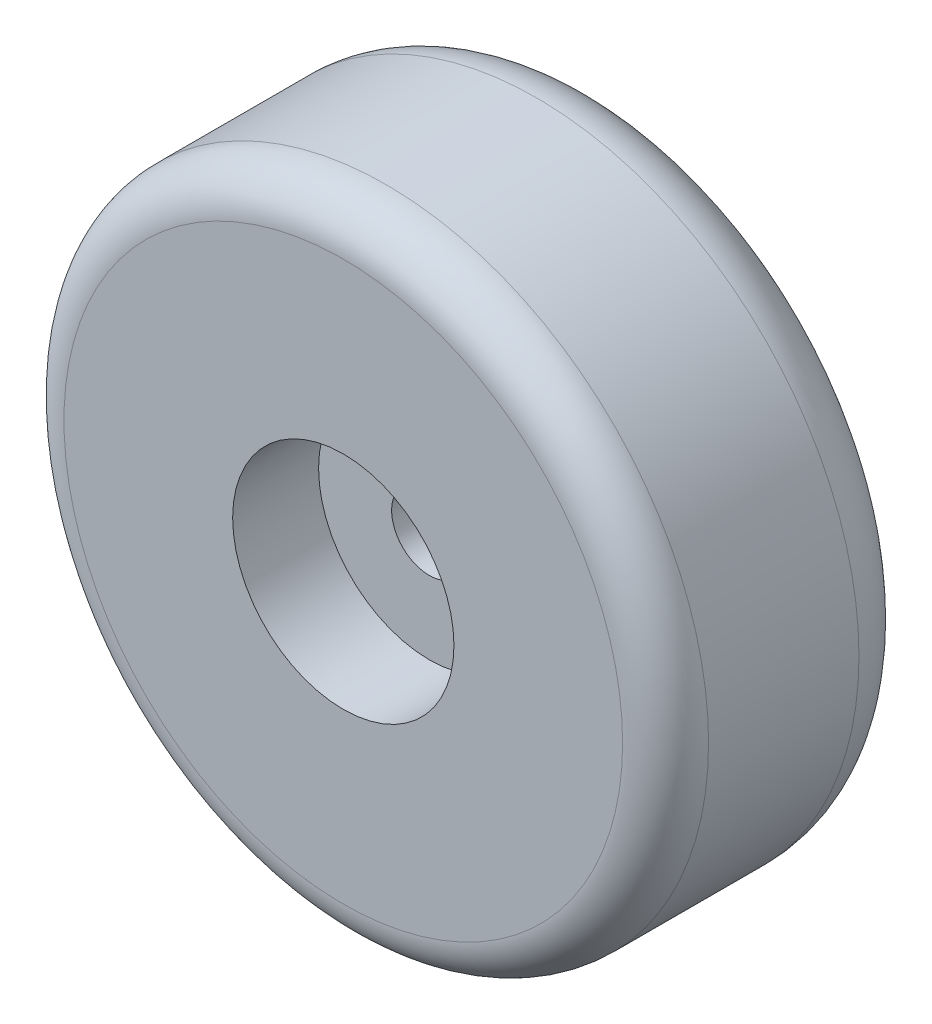
SolidWorks part; units mm, degrees
ref_plane "Спереди" through (0, 0, 0) normal (0, 0, 1) x (1, 0, 0)
ref_plane "Сверху" through (0, 0, 0) normal (0, 1, 0) x (1, 0, 0)
ref_plane "Справа" through (0, 0, 0) normal (1, 0, 0) x (0, 0, -1)
sketch "Эскиз1" plane through (0, 0, 0) normal (0, 0, 1) x (1, 0, 0)
  circle A0 centre (0, 0) radius 1.75
  circle A1 centre (0, 0) radius 15
  dimension "D1" = 3.5
  dimension "D2" = 30
extrude "Бобышка-Вытянуть1" add sketch "Эскиз1" along normal blind 12
sketch "Эскиз2" plane through (0, 0, 12) normal (0, 0, 1) x (1, 0, 0)
  circle A0 centre (0, 0) radius 5.15
  dimension "D1" = 10.3
extrude "Вырез-Вытянуть1" cut sketch "Эскиз2" against normal blind 4
fillet "Скругление1" radius 2 1 edges at (15, 0, 12)
fillet "Скругление2" radius 3 1 edges at (15, 0, 0)
